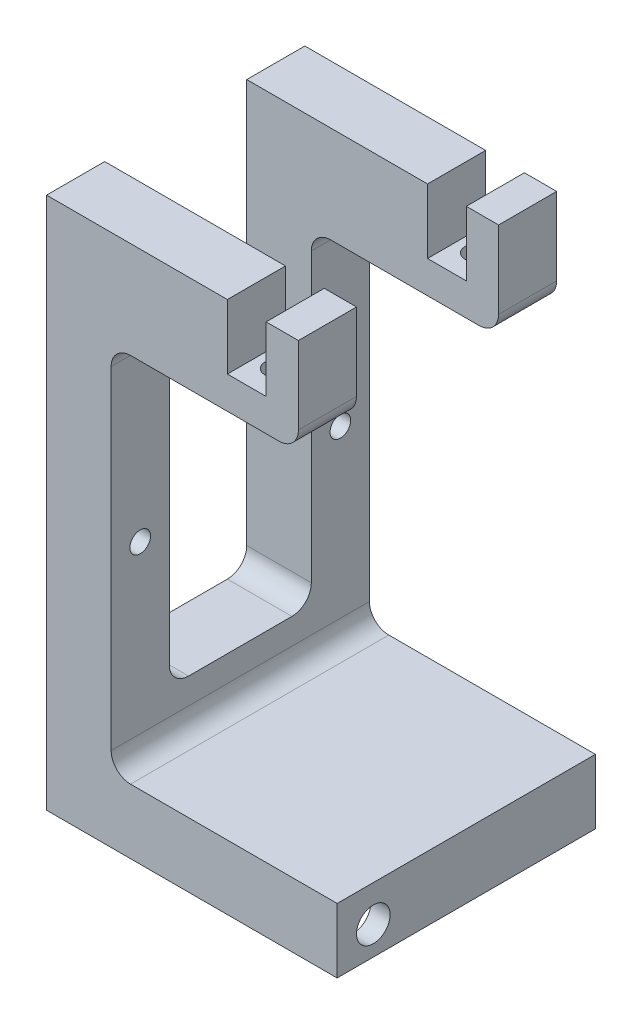
SolidWorks part; units mm, degrees
ref_plane "Front Plane" through (0, 0, 0) normal (0, 0, 1) x (1, 0, 0)
ref_plane "Top Plane" through (0, 0, 0) normal (0, 1, 0) x (1, 0, 0)
ref_plane "Right Plane" through (0, 0, 0) normal (1, 0, 0) x (0, 0, -1)
sketch "Sketch1" plane through (0, 0, 0) normal (0, 0, 1) x (1, 0, 0)
  line L0 (10, 10) -> (45, 10)
  line L1 (0, 0) -> (45, 0)
  line L2 (0, 0) -> (0, 82.5)
  line L3 (0, 82.5) -> (28, 82.5)
  line L5 (10, 10) -> (10, 67.5)
  line L6 (10, 67.5) -> (39, 67.5)
  line L8 (45, 10) -> (45, 0)
  line L19 (39, 82.5) -> (39, 67.5)
  line L20 (28, 82.5) -> (34, 82.5) construction
  line L21 (28, 82.5) -> (34, 82.5) construction
  line L22 (28, 82.5) -> (28, 72.5)
  line L23 (28, 72.5) -> (34, 72.5)
  line L24 (34, 82.5) -> (34, 72.5)
  line L25 (34, 82.5) -> (39, 82.5)
  dimension "D2" = 82.5
  dimension "D3" = 39
  dimension "D4" = 45
  dimension "D5" = 5
  dimension "D6" = 6
  dimension "D7" = 10
  dimension "D1" = 10
  dimension "D8" = 15
  dimension "D9" = 10
extrude "Boss-Extrude1" add sketch "Sketch1" along normal blind 40
sketch "Sketch2" plane through (0, 0, 0) normal (-1, 0, 0) x (0, 0, 1)
  line L0 (40, 82.5) -> (0, 82.5) construction
  line L1 (9, 82.5) -> (31, 82.5)
  line L2 (9, 82.5) -> (9, 17)
  line L3 (9, 17) -> (31, 17)
  line L4 (31, 82.5) -> (31, 17)
  line L5 (40, 0) -> (0, 0) construction
  point P9 (20, 0)
  point P10 (20, 17)
  dimension "D1" = 17
  dimension "D2" = 22
extrude "Cut-Extrude1" cut sketch "Sketch2" against normal through all
sketch "Sketch4" plane through (0, 72.5, 0) normal (0, 1, 0) x (1, 0, 0)
  line L0 (31, -31) -> (31, -40) construction
  line L1 (34, -31) -> (28, -31) construction
  line L2 (34, -40) -> (28, -40) construction
  line L3 (0, -20) -> (45, -20) construction
  line L4 (0, -9) -> (0, -31) construction
  line L5 (45, -40) -> (45, 0) construction
  circle A0 centre (31, -35.5) radius 1.7
  circle A1 centre (31, -4.5) radius 1.7
  dimension "D1" = 3.4
extrude "Cut-Extrude2" cut sketch "Sketch4" against normal up to next
sketch "Sketch7" plane through (45, 0, 0) normal (1, 0, 0) x (0, 0, -1)
  line L1 (-40, 0) -> (-40, 10) construction
  line L2 (-40, 10) -> (0, 10) construction
  circle A0 centre (-34.4, 4.4) radius 2.6
  dimension "D1" = 5.2
  dimension "D2" = 5.6
  dimension "D3" = 5.6
extrude "Cut-Extrude3" cut sketch "Sketch7" against normal blind 10
fillet "Fillet1" radius 3 3 edges at (10, 10, 20) (5, 17, 31) (5, 17, 9)
fillet "Fillet2" radius 3 4 edges at (39, 67.5, 4.5) (39, 67.5, 35.5) (10, 67.5, 35.5) (10, 67.5, 4.5)
sketch "Sketch8" plane through (0, 0, 0) normal (0, -1, 0) x (1, 0, 0)
  line L8 (3, 3) -> (42, 3)
  line L9 (42, 3) -> (42, 37)
  line L10 (42, 37) -> (3, 37)
  line L11 (3, 37) -> (3, 3)
  line L12 (3, 3) -> (42, 3)
  line L13 (42, 3) -> (42, 37)
  line L14 (42, 37) -> (3, 37)
  line L15 (3, 37) -> (3, 3)
  dimension "D1" = 3
extrude "Cut-Extrude4" cut sketch "Sketch8" against normal blind 7
sketch "Sketch9" plane through (10, 0, 0) normal (1, 0, 0) x (0, 0, -1)
  line L0 (-4.5, 64.5) -> (-4.5, 13) construction
  line L1 (0, 64.5) -> (-9, 64.5) construction
  line L2 (-40, 13) -> (0, 13) construction
  line L3 (-20, 17) -> (-20, 82.5748) construction
  line L4 (-12, 17) -> (-28, 17) construction
  circle A0 centre (-4.5, 38.75) radius 1.6
  circle A1 centre (-35.5, 38.75) radius 1.6
  dimension "D1" = 3.2
extrude "Cut-Extrude5" cut sketch "Sketch9" against normal up to next
